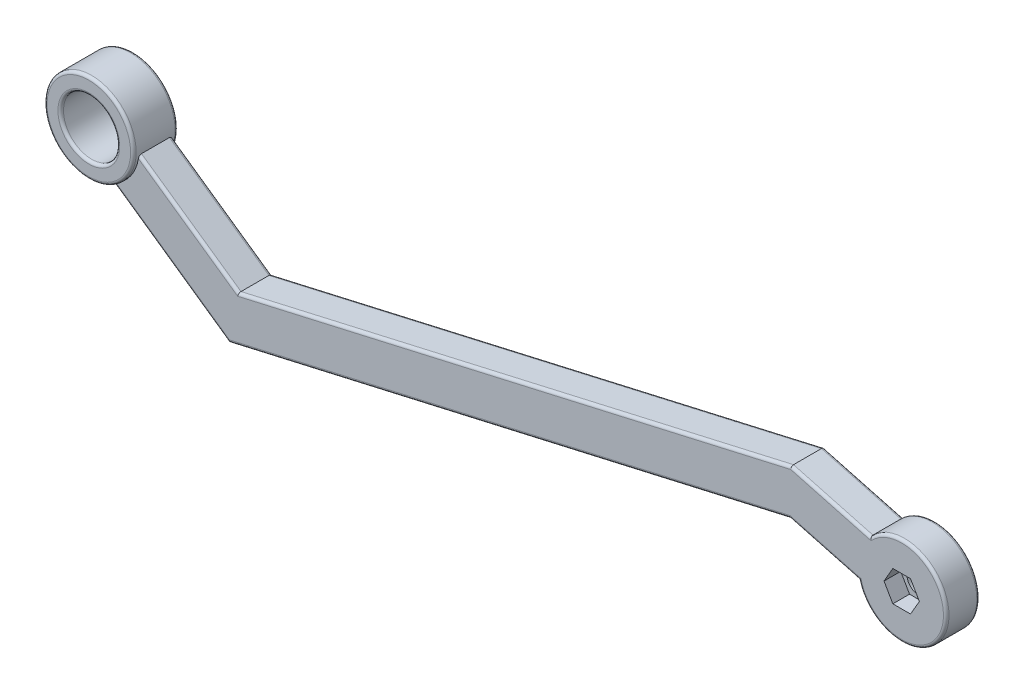
SolidWorks part; units mm, degrees
ref_plane "前视基准面" through (0, 0, 0) normal (0, 0, 1) x (1, 0, 0)
ref_plane "上视基准面" through (0, 0, 0) normal (0, 1, 0) x (1, 0, 0)
ref_plane "右视基准面" through (0, 0, 0) normal (1, 0, 0) x (0, 0, -1)
other "Configuration Table"
sketch "草图1" plane through (0, 0, 0) normal (0, 0, 1) x (1, 0, 0)
  line L0 (0, 0) -> (-145, 0) construction
  line L3 (-145, 0) -> (-120, -17.5052) construction
  line L4 (-120, -17.5052) -> (-20, 5.359) construction
  line L5 (-20, 5.359) -> (0, 0) construction
  line L7 (-142.7057, 3.2766) -> (-119.1604, -13.21)
  line L8 (-147.2943, -3.2766) -> (-120.8396, -21.8004)
  line L10 (-120.8396, -21.8004) -> (-20.0763, 1.2383)
  line L11 (-20.0763, 1.2383) -> (-1.0353, -3.8637)
  line L12 (1.0353, 3.8637) -> (-19.9237, 9.4796)
  line L13 (-19.9237, 9.4796) -> (-119.1604, -13.21)
  arc A0 (-5.6569, 5.6569) -> (-7.7274, -2.0706) centre (0, 0) cw
  arc A1 (-137.0304, -0.6972) -> (-141.6191, -7.2505) centre (-145, 0) ccw
  circle A2 centre (-145, 0) radius 4
  circle A3 centre (0, 0) radius 4
  circle A4 centre (-145, 0) radius 5.05
  circle A5 centre (0, 0) radius 2.05
  dimension "D2" = 8
  dimension "D3" = 8
  dimension "D6" = 10.1
  dimension "D7" = 4.1
  dimension "D1" = 145
  dimension "D4" = 25
  dimension "D5" = 35
  dimension "D8" = 15
  dimension "D9" = 20
  dimension "D10" = 4
  dimension "D11" = 4
extrude "凸台-拉伸1" add sketch "草图1" along normal mid plane 6 contours A3 L12 L13 L7 A2 L8 L10 L11 | A3 L11 A0 L12 | A4 L7 A1 L8 | A3 A5 region at (-73.7949, -5.6922, 0) region at (-138.4757, 0.591, 0) region at (7.5107, -2.0125, 0) region at (3.0837, 2.3662, 0)
ref_axis "后基准轴" through (0, 0, 0) along (0, 0, 1)
ref_axis "前基准轴" through (-145, 0, 0) along (0, 0, 1)
sketch "草图2" plane through (0, 0, 0) normal (0, 0, 1) x (1, 0, 0)
  circle A0 centre (-145, 0) radius 5.05
  circle A1 centre (-145, 0) radius 8
  circle A2 centre (-145, 0) radius 5.05 construction
  arc A3 (-137.0304, -0.6972) -> (-141.6191, -7.2505) centre (-145, 0) ccw construction
extrude "凸台-拉伸2" add sketch "草图2" along normal blind 4 and the other way blind 4 contours A1 A0 region at (-152.7737, 0, 0)
sketch "草图3" plane through (0, 0, 3) normal (0, 0, 1) x (1, 0, 0)
  line L1 (1.5877, -2.75) -> (3.1754, 0)
  line L2 (3.1754, 0) -> (1.5877, 2.75)
  line L3 (1.5877, 2.75) -> (-1.5877, 2.75)
  line L4 (-1.5877, 2.75) -> (-3.1754, 0)
  line L5 (-3.1754, 0) -> (-1.5877, -2.75)
  line L6 (-1.5877, -2.75) -> (1.5877, -2.75)
  circle A0 centre (0, 0) radius 2.75 construction
  dimension "D1" = 5.5
extrude "切除-拉伸1" cut sketch "草图3" against normal blind 3
fillet "圆角1" radius 0.5 19 edges at (-13.9018, -0.4161, -3) (-131.2293, -14.5254, -3) (-70.458, -10.281, -3) (-69.542, -1.8652, 3) (-128.0954, -6.9536, 3) (-131.2293, -14.5254, 3) (-137, 0, 4) (-137, 0, -4) (-128.0954, -6.9536, -3) (-69.542, -1.8652, -3) (7.7274, -2.0706, -3) (-12.7903, 7.5683, -3) (-12.7903, 7.5683, 3) (7.7274, -2.0706, 3) (-13.9018, -0.4161, 3) (-70.458, -10.281, 3) (2.05, 0, -3) (-139.95, 0, -4) (-139.95, 0, 4)
